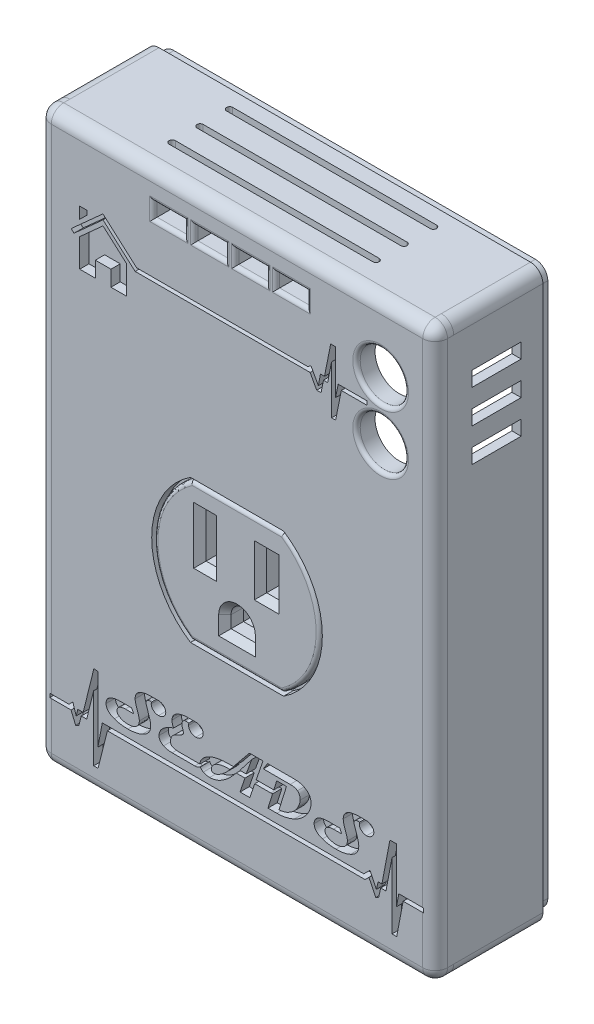
SolidWorks part; units mm, degrees
ref_plane "Front Plane" through (0, 0, 0) normal (0, 0, 1) x (1, 0, 0)
ref_plane "Top Plane" through (0, 0, 0) normal (0, 1, 0) x (1, 0, 0)
ref_plane "Right Plane" through (0, 0, 0) normal (1, 0, 0) x (0, 0, -1)
sketch "Sketch1" plane through (0, 0, 0) normal (0, 0, 1) x (1, 0, 0)
  line L0 (-40.64, -58.42) -> (40.64, -58.42)
  line L1 (-40.64, 58.42) -> (40.64, 58.42)
  line L2 (-40.64, 58.42) -> (-40.64, -58.42)
  line L3 (-40.64, -58.42) -> (40.64, -58.42) construction
  line L4 (40.64, 58.42) -> (40.64, -58.42)
  line L5 (-40.64, 58.42) -> (40.64, -58.42) construction
  line L6 (-40.64, -58.42) -> (40.64, 58.42) construction
  line L7 (-40.64, 58.42) -> (40.64, 58.42) construction
  line L9 (-40.64, 0) -> (40.64, 0) construction
  point P0 (0, 0)
sketch "Sketch4" plane through (0, 0, 0) normal (0, 0, 1) x (1, 0, 0)
  line L1 (-36.195, 56.515) -> (36.195, 56.515)
  line L2 (-38.735, 53.975) -> (-38.735, -53.975)
  line L3 (-36.195, -56.515) -> (36.195, -56.515)
  line L4 (38.735, 53.975) -> (38.735, -53.975)
  arc A0 (-38.735, 53.975) -> (-36.195, 56.515) centre (-36.195, 53.975) ccw
  arc A1 (36.195, 56.515) -> (38.735, 53.975) centre (36.195, 53.975) ccw
  arc A2 (-36.195, -56.515) -> (-38.735, -53.975) centre (-36.195, -53.975) ccw
  arc A3 (38.735, -53.975) -> (36.195, -56.515) centre (36.195, -53.975) ccw
  dimension "D1" = 5.08
sketch "Sketch5" plane through (0, 0, 0) normal (0, 0, 1) x (1, 0, 0)
  line L1 (-38.735, 53.975) -> (-38.735, 18.415) construction
  line L2 (38.735, 53.975) -> (38.735, 18.415) construction
  line L3 (-38.735, 18.415) -> (38.735, 18.415) construction
  line L4 (-25.4, 53.594) -> (-25.4, 56.515)
  line L6 (-25.4, 56.515) -> (-30.48, 56.515)
  line L7 (-30.48, 56.515) -> (-30.48, 53.594)
  line L8 (25.4, 53.594) -> (25.4, 56.515)
  line L9 (25.4, 56.515) -> (30.48, 56.515)
  line L10 (30.48, 56.515) -> (30.48, 53.594)
  line L11 (-35.56, 23.495) -> (-38.735, 23.495)
  line L12 (-38.735, 23.495) -> (-38.735, 18.415)
  line L13 (-38.735, 18.415) -> (-35.56, 18.415)
  line L14 (35.56, 23.495) -> (38.735, 23.114)
  line L15 (38.735, 23.114) -> (38.735, 18.415)
  line L16 (38.735, 18.415) -> (35.56, 18.415)
  arc A0 (-30.48, 53.594) -> (-25.4, 53.594) centre (-27.94, 53.594) ccw
  arc A1 (-35.56, 18.415) -> (-35.56, 23.495) centre (-35.56, 20.955) ccw
  arc A2 (25.4, 53.594) -> (30.48, 53.594) centre (27.94, 53.594) ccw
  arc A3 (35.56, 23.495) -> (35.56, 18.415) centre (35.56, 20.955) ccw
  dimension "D1" = 5.08
  dimension "D3" = 10.795
  dimension "D4" = 10.795
  dimension "D6" = 2.54
  dimension "D7" = 3.175
  dimension "D8" = 3.175
extrude "Case Extrude" add sketch "Sketch1" against normal blind 20.32
extrude "Case Cut" cut sketch "Sketch4" against normal blind 25.4
extrude "DaughterBoard Extrude" add sketch "Sketch5" against normal blind 9.525
sketch "Sketch6" plane through (0, 0, 0) normal (0, 0, 1) x (1, 0, 0)
  circle A0 centre (-27.94, 53.594) radius 0.9525
  circle A1 centre (-35.56, 20.955) radius 0.9525
  circle A2 centre (35.56, 20.955) radius 0.9525
  circle A3 centre (27.94, 53.594) radius 0.9525
  dimension "D1" = 1.905
extrude "DaughterBoard Holes" cut sketch "Sketch6" against normal blind 9.525
sketch "Sketch8" plane through (0, 0, 0) normal (0, 0, 1) x (1, 0, 0)
  circle A0 centre (-36.195, 53.975) radius 0.9525
  circle A1 centre (-36.195, -53.975) radius 0.9525
  circle A2 centre (36.195, 53.975) radius 0.9525
  circle A3 centre (36.195, -53.975) radius 0.9525
  dimension "D1" = 1.905
extrude "Cut-Extrude6" cut sketch "Sketch8" against normal through all
fillet "Fillet2" radius 2.54 1 edges at (40.64, 58.42, -10.16) type face fillet first side face at (40.64, 0, -10.16) second side face at (0, 58.42, -10.16)
fillet "Fillet3" radius 2.54 1 edges at (-40.64, 58.42, -10.16) type face fillet first side face at (-40.64, 0, -10.16) second side face at (-1.27, 58.42, -10.16)
fillet "Fillet4" radius 2.54 1 edges at (-40.64, -58.42, -10.16) type face fillet first side face at (-40.64, -1.27, -10.16) second side face at (0, -58.42, -10.16)
fillet "Fillet5" radius 2.54 1 edges at (40.64, -58.42, -10.16) type face fillet first side face at (1.27, -58.42, -10.16) second side face at (40.64, -1.27, -10.16)
ref_plane "Left Side Plane" through (-40.64, 0, 0) normal (-1, 0, 0) x (0, 0, 1)
sketch "Sketch11" plane through (-40.64, 0, 0) normal (-1, 0, 0) x (0, 0, 1)
  line L0 (-25.4, 33.3539) -> (-25.4, 27.7659)
  line L1 (-23.3153, 53.4199) -> (-2.9953, 53.4199) construction
  line L2 (-25.4, 21.6699) -> (-25.4, 16.0819)
  line L3 (-20.32, 55.88) -> (0, 55.88)
  line L4 (-11.43, 53.4199) -> (-11.43, 1.9849) construction
  line L6 (-22.0453, 17.3087) -> (-1.7253, 17.3087) construction
  line L7 (-22.8236, 33.3539) -> (-25.4, 33.3539)
  line L8 (-22.8236, 27.7659) -> (-25.4, 27.7659)
  line L9 (-17.5768, 35.4697) -> (-17.5768, 51.2722) construction
  line L10 (-25.4, 33.3539) -> (-25.4, 27.7659)
  line L11 (-22.8236, 21.6699) -> (-25.4, 21.6699)
  line L12 (-22.8236, 16.0819) -> (-25.4, 16.0819)
  arc A1 (-22.8236, 27.7659) -> (-22.8236, 33.3539) centre (-22.8236, 30.5599) ccw
  arc A2 (-22.8236, 16.0819) -> (-22.8236, 21.6699) centre (-22.8236, 18.8759) ccw
  circle A3 centre (-13.4493, 35.4697) radius 4.1275
  dimension "D1" = 5.588
  dimension "D6" = 8.255
  dimension "D3" = 22.86
  dimension "D5" = 11.684
  dimension "D8" = 18.161
  dimension "D9" = 6.1468
extrude "Cut-Extrude7" cut sketch "Sketch11" against normal blind 2.032 contours A3
chamfer "Chamfer1" distance 0.635 angle 45 1 edges at (-40.64, 35.4697, -9.3218)
chamfer "Chamfer2" distance 0.762 angle 45 1 edges at (-38.735, 31.3422, -13.4493)
ref_plane "Plane1" through (0, 0, -20.32) normal (0, 0, -1) x (-1, 0, 0)
sketch "Sketch12" plane through (0, 0, -20.32) normal (0, 0, -1) x (-1, 0, 0)
  line L0 (-40.64, -58.42) -> (40.64, -58.42)
  line L1 (-40.64, 58.42) -> (40.64, 58.42)
  line L2 (-40.64, 58.42) -> (-40.64, -58.42)
  line L3 (-40.64, -58.42) -> (40.64, -58.42) construction
  line L4 (40.64, 58.42) -> (40.64, -58.42)
  line L5 (-40.64, 58.42) -> (40.64, -58.42) construction
  line L6 (-40.64, -58.42) -> (40.64, 58.42) construction
  line L7 (-40.64, 58.42) -> (40.64, 58.42) construction
  line L8 (-39.624, 57.404) -> (39.624, 57.404)
  line L9 (-40.64, 0) -> (40.64, 0) construction
  line L10 (39.624, 57.404) -> (39.624, -57.404)
  line L11 (-39.624, -57.404) -> (39.624, -57.404)
  line L12 (-39.624, 57.404) -> (-39.624, -57.404)
  point P0 (0, 0)
  dimension "D1" = 1.016
extrude "Cut-Extrude9" cut sketch "Sketch12" against normal blind 2.032
fillet "Fillet7" radius 2.54 1 edges at (-39.624, 57.404, -19.304) type face fillet first side face at (-39.624, 0, -19.304) second side face at (0, 57.404, -19.304)
fillet "Fillet8" radius 2.54 1 edges at (-39.624, -57.404, -19.304) type face fillet first side face at (-39.624, -1.27, -19.304) second side face at (0, -57.404, -19.304)
fillet "Fillet9" radius 2.54 1 edges at (39.624, -57.404, -19.304) type face fillet first side face at (1.27, -57.404, -19.304) second side face at (39.624, 0, -19.304)
fillet "Fillet10" radius 2.54 1 edges at (39.624, 57.404, -19.304) type face fillet first side face at (39.624, 1.27, -19.304) second side face at (1.27, 57.404, -19.304)
ref_plane "Plane2" through (0, 58.42, 0) normal (0, 1, 0) x (1, 0, 0)
sketch "Sketch13" plane through (0, 58.42, 0) normal (0, 1, 0) x (1, 0, 0)
  line L0 (-19.9314, 2.8156) -> (21.8732, 2.8156) construction
  line L1 (-19.9314, 3.4506) -> (21.8732, 3.4506)
  line L2 (-19.9314, 2.1806) -> (21.8732, 2.1806)
  line L3 (-19.9314, 8.5538) -> (21.8732, 8.5538) construction
  line L4 (-19.9314, 9.1888) -> (21.8732, 9.1888)
  line L5 (-19.9314, 7.9188) -> (21.8732, 7.9188)
  line L6 (-19.9314, 14.6091) -> (21.8732, 14.6091) construction
  line L7 (-19.9314, 15.2441) -> (21.8732, 15.2441)
  line L8 (-19.9314, 13.9741) -> (21.8732, 13.9741)
  arc A0 (-19.9314, 3.4506) -> (-19.9314, 2.1806) centre (-19.9314, 2.8156) ccw
  arc A1 (21.8732, 2.1806) -> (21.8732, 3.4506) centre (21.8732, 2.8156) ccw
  arc A2 (-19.9314, 9.1888) -> (-19.9314, 7.9188) centre (-19.9314, 8.5538) ccw
  arc A3 (21.8732, 7.9188) -> (21.8732, 9.1888) centre (21.8732, 8.5538) ccw
  arc A4 (-19.9314, 15.2441) -> (-19.9314, 13.9741) centre (-19.9314, 14.6091) ccw
  arc A5 (21.8732, 13.9741) -> (21.8732, 15.2441) centre (21.8732, 14.6091) ccw
  point P2 (0.9709, 2.8156)
  point P7 (0.9709, 8.5538)
  point P14 (0.9709, 14.6091)
extrude "Cut-Extrude10" cut sketch "Sketch13" against normal through all
sketch "Sketch25" plane through (40.64, 0, 0) normal (1, 0, 0) x (0, 0, -1)
  line L0 (8.8181, 44.704) -> (8.8181, 40.894) construction
  line L1 (3.7987, 47.752) -> (13.8375, 47.752)
  line L2 (3.7987, 47.752) -> (3.7987, 44.704)
  line L3 (3.7987, 44.704) -> (13.8375, 44.704)
  line L4 (13.8375, 47.752) -> (13.8375, 44.704)
  line L5 (3.7987, 40.894) -> (13.8375, 40.894)
  line L6 (3.7987, 40.894) -> (3.7987, 37.846)
  line L7 (3.7987, 37.846) -> (13.8375, 37.846)
  line L8 (13.8375, 40.894) -> (13.8375, 37.846)
  line L9 (3.7987, 34.036) -> (13.8375, 34.036)
  line L10 (3.7987, 34.036) -> (3.7987, 30.988)
  line L11 (3.7987, 30.988) -> (13.8375, 30.988)
  line L12 (13.8375, 34.036) -> (13.8375, 30.988)
  line L13 (8.8181, 37.846) -> (8.8181, 34.036) construction
  line L14 (9.144, 55.88) -> (9.144, 47.752) construction
  line L15 (18.288, 55.88) -> (0, 55.88) construction
  dimension "D1" = 8.128
  dimension "D2" = 3.048
  dimension "D3" = 3.81
ref_plane "Plane3" through (0, 0, 0) normal (0, 0, 1) x (1, 0, 0)
sketch "Sketch14" plane through (0, 0, 0) normal (0, 0, 1) x (1, 0, 0)
  line L0 (-40.64, -58.42) -> (40.64, -58.42)
  line L1 (-40.64, 58.42) -> (40.64, 58.42)
  line L2 (-40.64, 58.42) -> (-40.64, -58.42)
  line L3 (-40.64, -58.42) -> (40.64, -58.42) construction
  line L4 (40.64, 58.42) -> (40.64, -58.42)
  line L5 (-40.64, 58.42) -> (40.64, -58.42) construction
  line L6 (-40.64, -58.42) -> (40.64, 58.42) construction
  line L7 (-40.64, 58.42) -> (40.64, 58.42) construction
  line L9 (-40.64, 0) -> (40.64, 0) construction
  point P0 (0, 0)
extrude "Boss-Extrude1" add sketch "Sketch14" along normal blind 3.81 separate body
sketch "Sketch15" plane through (0, 0, 0) normal (0, 0, 1) x (1, 0, 0)
  line L0 (2.794, 52.4985) -> (2.794, 49.4505) construction
  line L1 (-17.145, 52.4985) -> (-10.795, 52.4985)
  line L2 (-17.145, 52.4985) -> (-17.145, 49.4505)
  line L3 (-17.145, 49.4505) -> (-10.795, 49.4505)
  line L4 (-10.795, 52.4985) -> (-10.795, 49.4505)
  line L5 (-8.763, 52.4985) -> (-2.413, 52.4985)
  line L6 (-8.763, 52.4985) -> (-8.763, 49.4505)
  line L7 (-8.763, 49.4505) -> (-2.413, 49.4505)
  line L8 (-2.413, 52.4985) -> (-2.413, 49.4505)
  line L9 (-0.381, 52.4985) -> (5.969, 52.4985)
  line L10 (-0.381, 52.4985) -> (-0.381, 49.4505)
  line L11 (-0.381, 49.4505) -> (5.969, 49.4505)
  line L12 (5.969, 52.4985) -> (5.969, 49.4505)
  line L13 (8.001, 52.4985) -> (14.351, 52.4985)
  line L14 (8.001, 52.4985) -> (8.001, 49.4505)
  line L15 (8.001, 49.4505) -> (14.351, 49.4505)
  line L16 (14.351, 52.4985) -> (14.351, 49.4505)
  line L17 (-5.588, 52.4985) -> (-5.588, 49.4505) construction
  line L18 (-13.97, 52.4985) -> (-13.97, 49.4505) construction
  line L19 (-17.145, 50.9745) -> (-17.8007, 50.9745) construction
  line L21 (14.351, 50.9745) -> (15.0067, 50.9745) construction
  line L23 (-13.97, 52.4985) -> (-13.97, 56.515) construction
  line L29 (38.3068, 56.515) -> (-38.1, 56.515) construction
  line L34 (38.735, 53.975) -> (38.735, -51.7067) construction
  line L36 (11.176, 52.4985) -> (11.176, 49.4505) construction
  line L37 (8.001, 50.9745) -> (14.351, 50.9745) construction
  line L38 (-17.145, 50.9745) -> (-10.795, 50.9745) construction
  line L39 (-8.763, 50.9745) -> (-2.413, 50.9745) construction
  line L40 (-0.381, 50.9745) -> (5.969, 50.9745) construction
  line L43 (15.0067, 44.8251) -> (15.0067, 54.691) construction
  line L44 (-38.735, 53.975) -> (-38.735, 33.0818) construction
  circle A0 centre (29.464, 44.831) radius 4.953
  circle A1 centre (29.464, 32.893) radius 4.953
  dimension "D3" = 9.906
  dimension "D8" = 24.765
  dimension "D1" = 6.35
  dimension "D2" = 3.048
  dimension "D4" = 11.938
  dimension "D6" = 5.5405
  dimension "D7" = 9.271
  dimension "D11" = 8.382
  dimension "D12" = 8.382
  dimension "D13" = 8.382
extrude "Cut-Extrude11" cut sketch "Sketch15" along normal through all
sketch "Sketch16" plane through (0, 0, 0) normal (0, 0, 1) x (1, 0, 0)
  line L0 (-4.8133, -2.5527) -> (5.461, -2.5527) construction
  line L13 (-36.195, -51.435) -> (36.195, -51.435) construction
  line L14 (-2.4892, -14.097) -> (-2.4892, -16.5862)
  line L15 (-2.4892, -16.5862) -> (2.4892, -16.5862)
  line L16 (2.4892, -14.097) -> (2.4892, -16.5862)
  line L17 (-2.4892, -11.6078) -> (2.4892, -16.5862) construction
  line L18 (-2.4892, -16.5862) -> (2.5639, -11.5331) construction
  line L19 (7.62, -2.5527) -> (38.735, -2.5527) construction
  line L21 (-7.3533, -2.5527) -> (-38.735, -2.5527) construction
  line L23 (0, 58.42) -> (0, -58.42) construction
  line L26 (7.3533, 1.4478) -> (7.3533, -6.5532)
  line L27 (7.3533, -6.5532) -> (4.8133, -6.5532)
  line L28 (-5.461, 2.032) -> (-7.62, 2.032)
  line L29 (-5.461, 2.032) -> (-5.461, -7.1374)
  line L30 (-7.62, 2.032) -> (-7.62, -7.1374)
  line L31 (-5.461, -7.1374) -> (-7.62, -7.1374)
  line L32 (7.3533, 1.4478) -> (4.8133, 1.4478)
  line L33 (4.8133, 1.4478) -> (4.8133, -6.5532)
  arc A0 (2.4892, -14.097) -> (-2.4892, -14.097) centre (0, -14.097) ccw
  point P0 (-6.0833, -2.5527)
  point P5 (6.5405, -2.5527)
  point P10 (0, -14.097)
  dimension "D6" = 4.9784
  dimension "D5" = 12.6238
  dimension "D8" = 37.338
  dimension "D9" = 31.115
extrude "Cut-Extrude12" cut sketch "Sketch16" along normal through all
sketch "Sketch18" plane through (0, 0, 0) normal (0, 0, 1) x (1, 0, 0)
  line L0 (11.3395, 3.8087) -> (0.8271, 3.8087)
  line L1 (0.8271, -8.9141) -> (0.8271, 3.8087)
  line L2 (-7.62, -7.1374) -> (-5.461, 2.032) construction
  line L3 (-5.461, 2.032) -> (-7.62, 2.032) construction
  line L4 (-7.62, 2.032) -> (-5.461, -7.1374) construction
  line L5 (4.8133, 1.4478) -> (7.3533, -6.5532) construction
  line L6 (4.8133, -6.5532) -> (7.3533, 1.4478) construction
  line L7 (-11.6632, 3.8087) -> (-1.4178, 3.8087)
  line L8 (11.3395, -8.9141) -> (0.8271, -8.9141)
  line L9 (11.3395, -8.9141) -> (11.3395, 3.8087)
  line L10 (-4.9784, -14.097) -> (-4.9784, -19.0754)
  line L11 (-4.9784, -19.0754) -> (4.9784, -19.0754)
  line L12 (4.9784, -19.0754) -> (4.9784, -14.097)
  line L16 (-3.7084, -14.097) -> (-3.7084, -17.8054)
  line L17 (-3.7084, -17.8054) -> (3.7084, -17.8054)
  line L18 (3.7084, -17.8054) -> (3.7084, -14.097)
  line L30 (10.3235, -7.8981) -> (1.8431, -7.8981)
  line L31 (10.3235, -7.8981) -> (10.3235, 2.7927)
  line L32 (10.3235, 2.7927) -> (1.8431, 2.7927)
  line L33 (1.8431, -7.8981) -> (1.8431, 2.7927)
  line L34 (10.3235, -7.8981) -> (1.8431, 2.7927) construction
  line L35 (10.3235, 2.7927) -> (1.8431, -7.8981) construction
  line L36 (-10.6472, -7.8981) -> (-2.4338, -7.8981)
  line L41 (39.37, -57.15) -> (39.37, 57.15)
  line L42 (39.37, 57.15) -> (-39.37, 57.15)
  line L43 (-39.37, 57.15) -> (-39.37, -57.15)
  line L44 (-39.37, -57.15) -> (39.37, -57.15)
  line L45 (-10.6472, -7.8981) -> (-10.6472, 2.7927)
  line L46 (-10.6472, 2.7927) -> (-2.4338, 2.7927)
  line L47 (-2.4338, -7.8981) -> (-2.4338, 2.7927)
  line L48 (-10.6472, -7.8981) -> (-2.4338, 2.7927) construction
  line L49 (-10.6472, 2.7927) -> (-2.4338, -7.8981) construction
  line L50 (-1.4178, -8.9141) -> (-1.4178, 3.8087)
  line L51 (-11.6632, -8.9141) -> (-1.4178, -8.9141)
  line L52 (-11.6632, -8.9141) -> (-11.6632, 3.8087)
  arc A2 (4.9784, -14.097) -> (-4.9784, -14.097) centre (0, -14.097) ccw
  arc A4 (3.7084, -14.097) -> (-3.7084, -14.097) centre (0, -14.097) ccw
  point P30 (6.0833, -2.5527)
  point P35 (-6.5405, -2.5527)
  dimension "D2" = 1.27
  dimension "D4" = 1.016
  dimension "D5" = 1.016
extrude "Boss-Extrude2" add sketch "Sketch18" against normal blind 10.16 contours L12 A2 L10 L11 | A4 L16 L17 L18 | L50 L7 L52 L51 | L47 L46 L45 L36 | L32 L33 L30 L31 | L0 L1 L8 L9
ref_plane "Plane4" through (0, 0, 3.81) normal (0, 0, 1) x (1, 0, 0)
sketch "Sketch19" plane through (0, 0, 0) normal (0, 0, 1) x (1, 0, 0)
  line L0 (2.794, 52.4985) -> (2.794, 49.4505) construction
  line L17 (-5.588, 52.4985) -> (-5.588, 49.4505) construction
  line L18 (-13.97, 52.4985) -> (-13.97, 49.4505) construction
  line L19 (-17.145, 50.9745) -> (-17.8007, 50.9745) construction
  line L20 (7.493, 53.0065) -> (14.859, 53.0065)
  line L21 (14.351, 50.9745) -> (15.0067, 50.9745) construction
  line L22 (14.859, 53.0065) -> (14.859, 48.9425)
  line L23 (-13.97, 52.4985) -> (-13.97, 56.515) construction
  line L24 (7.493, 48.9425) -> (14.859, 48.9425)
  line L25 (7.493, 53.0065) -> (7.493, 48.9425)
  line L26 (-0.889, 53.0065) -> (6.477, 53.0065)
  line L27 (6.477, 53.0065) -> (6.477, 48.9425)
  line L28 (-0.889, 48.9425) -> (6.477, 48.9425)
  line L29 (38.3068, 56.515) -> (-38.1, 56.515) construction
  line L30 (-0.889, 53.0065) -> (-0.889, 48.9425)
  line L31 (-9.271, 53.0065) -> (-1.905, 53.0065)
  line L32 (-1.905, 53.0065) -> (-1.905, 48.9425)
  line L33 (-9.271, 48.9425) -> (-1.905, 48.9425)
  line L34 (38.735, 53.975) -> (38.735, -51.7067) construction
  line L35 (-9.271, 53.0065) -> (-9.271, 48.9425)
  line L36 (11.176, 52.4985) -> (11.176, 49.4505) construction
  line L37 (8.001, 50.9745) -> (14.351, 50.9745) construction
  line L38 (-17.145, 50.9745) -> (-10.795, 50.9745) construction
  line L39 (-8.763, 50.9745) -> (-2.413, 50.9745) construction
  line L40 (-0.381, 50.9745) -> (5.969, 50.9745) construction
  line L41 (-17.653, 53.0065) -> (-10.287, 53.0065)
  line L42 (-10.287, 53.0065) -> (-10.287, 48.9425)
  line L43 (15.0067, 44.8251) -> (15.0067, 54.691) construction
  line L44 (-38.735, 53.975) -> (-38.735, 33.0818) construction
  line L45 (-17.653, 48.9425) -> (-10.287, 48.9425)
  line L46 (-17.653, 53.0065) -> (-17.653, 48.9425)
  line L47 (7.112, 53.3875) -> (7.112, 48.5615)
  line L48 (7.112, 48.5615) -> (15.24, 48.5615)
  line L49 (15.24, 53.3875) -> (15.24, 48.5615)
  line L50 (7.112, 53.3875) -> (15.24, 53.3875)
  line L51 (-1.27, 53.3875) -> (-1.27, 48.5615)
  line L52 (-1.27, 48.5615) -> (6.858, 48.5615)
  line L53 (6.858, 53.3875) -> (6.858, 48.5615)
  line L54 (-1.27, 53.3875) -> (6.858, 53.3875)
  line L55 (-9.652, 53.3875) -> (-9.652, 48.5615)
  line L56 (-9.652, 48.5615) -> (-1.524, 48.5615)
  line L57 (-1.524, 53.3875) -> (-1.524, 48.5615)
  line L58 (-9.652, 53.3875) -> (-1.524, 53.3875)
  line L59 (-18.034, 53.3875) -> (-18.034, 48.5615)
  line L60 (-18.034, 48.5615) -> (-9.906, 48.5615)
  line L61 (-9.906, 53.3875) -> (-9.906, 48.5615)
  line L62 (-18.034, 53.3875) -> (-9.906, 53.3875)
  dimension "D8" = 24.765
  dimension "D6" = 5.5405
  dimension "D9" = 0.381
  dimension "D11" = 8.382
  dimension "D12" = 8.382
  dimension "D13" = 8.382
extrude "Boss-Extrude3" add sketch "Sketch19" against normal blind 2.54
fillet "Fillet11" radius 2.54 4 edges at (40.64, -58.42, 1.905) (-40.64, -58.42, 1.905) (-40.64, 58.42, 1.905) (40.64, 58.42, 1.905)
fillet "Fillet12" radius 0.762 18 edges at (-17.145, 50.9745, 3.81) (-13.97, 49.4505, 3.81) (-13.97, 52.4985, 3.81) (-10.795, 50.9745, 3.81) (-8.763, 50.9745, 3.81) (-5.588, 49.4505, 3.81) (-5.588, 52.4985, 3.81) (-2.413, 50.9745, 3.81) (-0.381, 50.9745, 3.81) (2.794, 52.4985, 3.81) (5.969, 50.9745, 3.81) (2.794, 49.4505, 3.81) (8.001, 50.9745, 3.81) (11.176, 52.4985, 3.81) (14.351, 50.9745, 3.81) (11.176, 49.4505, 3.81) (34.417, 32.893, 3.81) (34.417, 44.831, 3.81)
chamfer "Chamfer3" distance 1.27 angle 45 12 edges at (-6.5405, -7.1374, 3.81) (-7.62, -2.5527, 3.81) (-6.5405, 2.032, 3.81) (-5.461, -2.5527, 3.81) (0, -16.5862, 3.81) (2.4892, -15.3416, 3.81) (-2.4892, -15.3416, 3.81) (0, -11.6078, 3.81) (6.0833, -6.5532, 3.81) (4.8133, -2.5527, 3.81) (6.0833, 1.4478, 3.81) (7.3533, -2.5527, 3.81)
sketch "Sketch20" plane through (0, 0, 3.81) normal (0, 0, 1) x (1, 0, 0)
  line L0 (-9.398, 6.9088) -> (9.398, 6.9088)
  line L1 (-9.398, -21.4122) -> (9.398, -21.4122)
  line L2 (-9.55, -21.9202) -> (9.55, -21.9202)
  line L3 (-9.55, 7.4168) -> (9.55, 7.4168)
  line L4 (-7.62, 2.032) -> (-5.461, 2.032) construction
  line L5 (-2.4384, -16.5354) -> (2.4384, -16.5354) construction
  line L6 (-6.5405, 2.032) -> (-6.5405, 6.9088) construction
  line L7 (0, -16.5354) -> (0, -21.4122) construction
  line L8 (0, -7.2517) -> (16.9954, -7.2517) construction
  line L14 (0, -7.2517) -> (-16.9954, -7.2517) construction
  arc A0 (-9.398, 6.9088) -> (-9.398, -21.4122) centre (0, -7.2517) ccw
  arc A1 (-9.55, 7.4168) -> (-9.55, -21.9202) centre (0, -7.2517) ccw
  arc A2 (9.398, -21.4122) -> (9.398, 6.9088) centre (0, -7.2517) ccw
  arc A3 (9.55, -21.9202) -> (9.55, 7.4168) centre (0, -7.2517) ccw
  dimension "D1" = 0.508
  dimension "D2" = 28.321
  dimension "D3" = 0.508
  dimension "D4" = 0.508
  dimension "D5" = 18.796
extrude "Cut-Extrude13" cut sketch "Sketch20" against normal blind 1.905 contours A1 L2 A3 L3 | A0 L1 A2 L0
fillet "Fillet13" radius 0.762 4 edges at (16.9954, -7.2517, 3.81) (0, 6.9088, 3.81) (0, -21.4122, 3.81) (-16.9954, -7.2517, 3.81)
fillet "Fillet14" radius 2.54 8 edges at (0, -58.42, 3.81) (-39.8961, -57.6761, 3.81) (-40.64, 0, 3.81) (-39.8961, 57.6761, 3.81) (0, 58.42, 3.81) (39.8961, 57.6761, 3.81) (39.8961, -57.6761, 3.81) (40.64, 0, 3.81)
sketch "Sketch21" plane through (0, 0, 3.81) normal (0, 0, 1) x (1, 0, 0)
  line L0 (-32.2727, 38.8156) -> (-32.2727, 33.0329)
  line L1 (-32.2727, 33.0329) -> (-29.0668, 33.0329)
  line L2 (-29.0668, 33.0329) -> (-29.0668, 36.2389)
  line L3 (-29.0668, 36.2389) -> (-25.8608, 36.2389)
  line L4 (-25.8608, 36.2389) -> (-25.8608, 33.0329)
  line L5 (-25.8608, 33.0329) -> (-22.6549, 33.0329)
  line L6 (-22.6549, 33.0329) -> (-22.6549, 38.8156)
  line L7 (-22.6549, 38.8156) -> (-27.4959, 43.1116)
  line L8 (-27.4959, 43.1116) -> (-32.2727, 38.8156)
  line L9 (-32.2727, 44.2368) -> (-32.2727, 41.8876)
  line L10 (-32.2727, 41.8876) -> (-30.7668, 43.3935)
  line L11 (-30.7668, 43.3935) -> (-30.7668, 44.2368)
  line L12 (-30.7668, 44.2368) -> (-32.2727, 44.2368)
  line L13 (-33.4695, 38.8068) -> (-27.4994, 44.1759)
  line L14 (-27.4994, 44.1759) -> (-20.9009, 38.3203)
  line L15 (-20.9009, 38.3203) -> (14.9947, 38.3203)
  line L17 (14.9947, 38.3203) -> (16.3406, 35.8462)
  line L18 (16.3406, 35.8462) -> (17.2442, 35.8462)
  line L19 (17.2442, 35.8462) -> (17.7368, 38.3203)
  line L20 (17.7368, 38.3203) -> (18.5861, 38.3203)
  line L21 (18.5861, 38.3203) -> (19.3988, 42.4016)
  line L22 (19.3988, 42.4016) -> (19.3988, 32.4626)
  line L23 (19.3988, 32.4626) -> (20.2305, 32.4626)
  line L24 (20.2305, 32.4626) -> (21.3969, 38.3203)
  line L25 (21.3969, 39.1178) -> (20.7481, 39.1178)
  line L26 (20.7481, 39.1178) -> (20.2183, 36.4569)
  line L27 (20.2183, 36.4569) -> (20.2183, 45.4974)
  line L28 (20.2183, 45.4974) -> (19.216, 45.4974)
  line L29 (19.216, 45.4974) -> (17.9457, 39.1178)
  line L30 (17.9457, 39.1178) -> (17.1158, 39.1178)
  line L31 (17.1158, 39.1178) -> (16.6796, 36.8151)
  line L32 (16.6796, 36.8151) -> (15.1974, 39.5397)
  line L33 (15.1974, 39.5397) -> (14.422, 39.1178)
  line L34 (14.422, 39.1178) -> (-20.6038, 39.1178)
  line L35 (-20.6038, 39.1178) -> (-27.5029, 45.2403)
  line L36 (-27.5029, 45.2403) -> (-34.0003, 39.397)
  line L37 (-34.0003, 39.397) -> (-33.4695, 38.8068)
  line L38 (21.3969, 39.1178) -> (26.6217, 39.1178)
  line L39 (26.6217, 39.1178) -> (26.6217, 38.3203)
  line L40 (26.6217, 38.3203) -> (21.3969, 38.3203)
extrude "Cut-Extrude14" cut sketch "Sketch21" against normal blind 1.905
sketch "Sketch22" plane through (0, 0, 3.81) normal (0, 0, 1) x (1, 0, 0)
  line L0 (-38.4164, -46.1613) -> (-34.0454, -46.1613)
  line L2 (-34.0454, -46.1613) -> (-33.1049, -48.4372)
  line L3 (-33.1049, -48.4372) -> (-32.4401, -48.1547)
  line L4 (-32.4401, -48.1547) -> (-31.951, -46.1888)
  line L5 (-31.951, -46.1888) -> (-30.8399, -46.1888)
  line L6 (-30.8399, -46.1888) -> (-29.4169, -40.4413)
  line L7 (-29.4169, -40.4413) -> (-29.4169, -53.763)
  line L8 (-29.4169, -53.763) -> (-28.5099, -53.763)
  line L9 (-28.5099, -53.763) -> (-26.5889, -46.1368)
  line L10 (-26.5889, -46.1368) -> (26.2603, -46.1368)
  line L11 (26.2603, -46.1368) -> (27.0615, -45.3433)
  line L12 (27.0615, -45.3433) -> (28.4578, -48.2483)
  line L13 (28.4578, -48.2483) -> (29.0403, -47.9683)
  line L14 (29.0403, -47.9683) -> (29.4865, -46.0196)
  line L15 (29.4865, -46.0196) -> (30.5525, -46.0196)
  line L16 (30.5525, -46.0196) -> (31.8017, -39.4554)
  line L17 (31.8017, -39.4554) -> (31.8017, -53.0245)
  line L18 (31.8017, -53.0245) -> (32.758, -53.0245)
  line L19 (32.758, -53.0245) -> (34.0812, -46.0714)
  line L20 (34.0812, -46.0714) -> (38.2177, -46.0714)
  line L21 (38.2177, -46.0714) -> (38.2177, -45.1957)
  line L22 (38.2177, -45.1957) -> (33.1949, -45.1957)
  line L23 (33.1949, -45.1957) -> (32.7105, -47.7414)
  line L24 (32.7105, -47.7414) -> (32.7105, -36.5707)
  line L25 (32.7105, -36.5707) -> (31.3621, -36.5707)
  line L26 (31.3621, -36.5707) -> (29.7207, -45.1961)
  line L27 (29.7207, -45.1961) -> (28.9407, -45.1961)
  line L28 (28.9407, -45.1961) -> (28.595, -46.706)
  line L29 (28.595, -46.706) -> (27.7473, -44.9425)
  line L30 (27.7473, -44.9425) -> (27.2832, -43.9768)
  line L31 (27.2832, -43.9768) -> (26.0122, -45.2478)
  line L32 (26.0122, -45.2478) -> (-27.6326, -45.2478)
  line L33 (-27.6326, -45.2478) -> (-28.5388, -50.0096)
  line L34 (-28.5388, -50.0096) -> (-28.5388, -36.6051)
  line L35 (-28.5388, -36.6051) -> (-29.3569, -36.4494)
  line L36 (-29.3569, -36.4494) -> (-31.5613, -45.3531)
  line L37 (-31.5613, -45.3531) -> (-32.6569, -45.3531)
  line L38 (-32.6569, -45.3531) -> (-32.9846, -46.683)
  line L39 (-32.9846, -46.683) -> (-33.6806, -44.5701)
  line L41 (-33.6806, -44.5701) -> (-34.4729, -45.3624)
  line L42 (-34.4729, -45.3624) -> (-38.4164, -45.3624)
  line L43 (-38.4164, -45.3624) -> (-38.4164, -46.1613)
extrude "Cut-Extrude15" cut sketch "Sketch22" against normal blind 1.905
sketch "Sketch24" plane through (0, 0, 3.81) normal (0, 0, 1) x (1, 0, 0)
  text T0 "SEADS" font "Magneto" height in points 28
extrude "Cut-Extrude16" cut sketch "Sketch24" against normal blind 1.905
extrude "Cut-Extrude17" cut sketch "Sketch25" against normal up to surface (1.905 mm away) up to face at (38.735, 10.3823, -7.4612)
